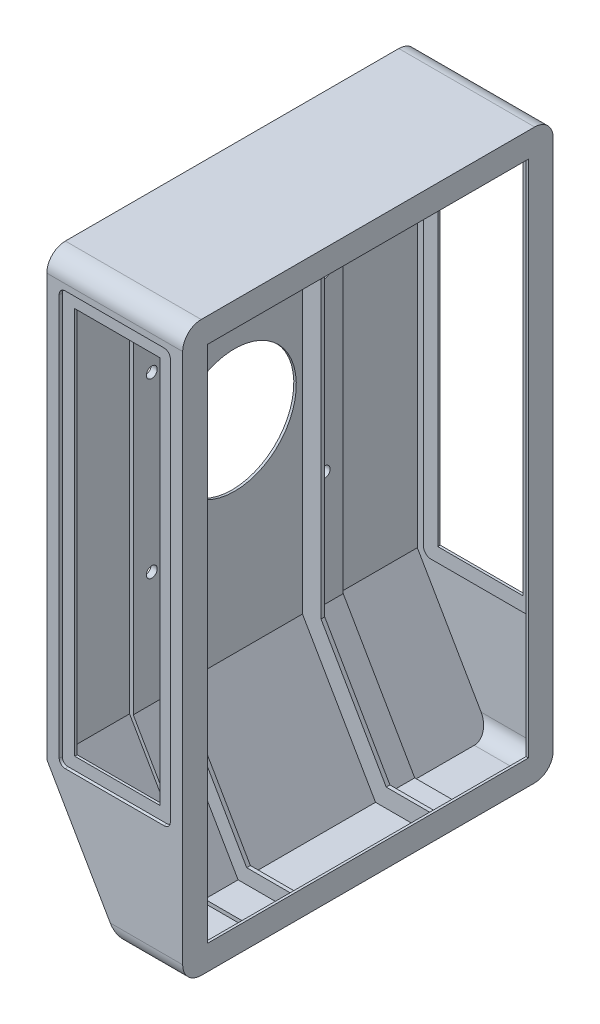
SolidWorks part; units mm, degrees
ref_plane "前视基准面" through (0, 0, 0) normal (0, 0, 1) x (1, 0, 0)
ref_plane "上视基准面" through (0, 0, 0) normal (0, 1, 0) x (1, 0, 0)
ref_plane "右视基准面" through (0, 0, 0) normal (1, 0, 0) x (0, 0, -1)
sketch "草图1" plane through (0, 0, 0) normal (0, 0, 1) x (1, 0, 0)
  line L1 (0, 227.2076) -> (-110, 227.2076)
  line L2 (0, 227.2076) -> (0, -232.7924)
  line L3 (0, -232.7924) -> (-110, -232.7924)
  line L4 (-110, 227.2076) -> (-110, -232.7924)
  dimension "D1" = 110
  dimension "D2" = 460
extrude "凸台-拉伸1" add sketch "草图1" against normal blind 300
chamfer "倒角1" distance 60 angle 60 1 edges at (-110, -232.7924, -150) first distance on face at (-55, -232.7924, -150)
chamfer "倒角2" [suppressed] distance 50 angle 30
ref_plane "基准面1" through (0, 0, -150) normal (0, 0, -1) x (-1, 0, 0)
ref_plane "基准面2" through (0, -2.7924, 0) normal (0, 1, 0) x (1, 0, 0)
fillet "圆角1" [suppressed] radius 20
fillet "圆角2" radius 15 4 edges at (-55, 227.2076, -300) (-25, -232.7924, -300) (-25, -232.7924, 0) (-55, 227.2076, 0)
sketch "草图2" plane through (0, 0, 0) normal (0, 0, 1) x (1, 0, 0)
  line L0 (0, -217.7924) -> (0, 212.2076) construction
  line L1 (-95, 207.2076) -> (-15, 207.2076)
  line L2 (-100, 202.2076) -> (-100, -122.7924)
  line L3 (-95, -127.7924) -> (-15, -127.7924)
  line L4 (-10, 202.2076) -> (-10, -122.7924)
  line L5 (-110, 212.2076) -> (-110, -128.8693) construction
  line L6 (-110, 227.2076) -> (0, 227.2076) construction
  arc A0 (-95, -127.7924) -> (-100, -122.7924) centre (-95, -122.7924) cw
  arc A1 (-15, -127.7924) -> (-10, -122.7924) centre (-15, -122.7924) ccw
  arc A2 (-100, 202.2076) -> (-95, 207.2076) centre (-95, 202.2076) cw
  arc A3 (-10, 202.2076) -> (-15, 207.2076) centre (-15, 202.2076) ccw
  point P14 (-10, -127.7924)
  point P19 (-10, 207.2076)
  dimension "D5" = 5
  dimension "D1" = 10
  dimension "D2" = 10
  dimension "D3" = 20
  dimension "D4" = 335
extrude "切除-拉伸1" cut sketch "草图2" against normal blind 2 draft 15
mirror "镜向1" about plane through (0, 0, -150) normal (0, 0, -1) of "切除-拉伸1"
shell "抽壳1" thickness 2
sketch "草图3" plane through (0, 0, 0) normal (1, 0, 0) x (0, 0, -1)
  line L2 (60.5, -2.7924) -> (-60.5, -2.7924) construction
  line L3 (20, -212.7924) -> (280, -212.7924)
  line L10 (20, -212.7924) -> (20, 207.2076)
  line L11 (20, 207.2076) -> (280, 207.2076)
  line L12 (280, -212.7924) -> (280, 207.2076)
  line L13 (20, -212.7924) -> (280, 207.2076) construction
  line L14 (20, 207.2076) -> (280, -212.7924) construction
  line L15 (150, -60.5) -> (150, 60.5) construction
  line L16 (285, 227.2076) -> (15, 227.2076) construction
  line L17 (300, -217.7924) -> (300, 212.2076) construction
  point P0 (150, -2.7924)
  dimension "D1" = 20
  dimension "D2" = 20
extrude "切除-拉伸2" cut sketch "草图3" against normal blind 3
sketch "草图4" plane through (0, 0, -298) normal (0, 0, -1) x (-1, 0, 0)
  line L0 (99.4641, 39.7076) -> (10.5359, 39.7076) construction
  line L1 (99.4641, 202.2076) -> (99.4641, -122.7924) construction
  line L2 (10.5359, -122.7924) -> (10.5359, 202.2076) construction
  line L3 (15, 206.6718) -> (95, 206.6718) construction
  line L4 (20.5359, -117.2565) -> (89.4641, -117.2565)
  line L5 (20.5359, -117.2565) -> (20.5359, 196.6718)
  line L6 (20.5359, 196.6718) -> (89.4641, 196.6718)
  line L7 (89.4641, -117.2565) -> (89.4641, 196.6718)
  line L8 (20.5359, -117.2565) -> (89.4641, 196.6718) construction
  line L9 (20.5359, 196.6718) -> (89.4641, -117.2565) construction
  point P6 (55, 39.7076)
  dimension "D1" = 10
  dimension "D2" = 10
extrude "切除-拉伸3" cut sketch "草图4" against normal blind 3
mirror "镜向2" about plane through (0, 0, -150) normal (0, 0, -1) of "切除-拉伸3"
ref_plane "基准面3" through (0, 0, -205) normal (0, 0, -1) x (-1, 0, 0)
sketch "草图6" plane through (0, 0, -205) normal (0, 0, -1) x (-1, 0, 0)
  line L6 (2, -230.7924) -> (48.8453, -230.7924)
  line L7 (48.8453, -230.7924) -> (108, -128.3334)
  line L8 (108, -128.3334) -> (108, 225.2076)
  line L9 (108, 225.2076) -> (2, 225.2076)
sketch "草图7" plane through (-2, 0, 0) normal (-1, 0, 0) x (0, 0, 1)
  line L0 (-15, -230.7924) -> (-285, -230.7924) construction
  line L1 (-235, -230.7924) -> (-205, -230.7924)
  line L2 (-235, -230.7924) -> (-235, -227.7924)
  line L3 (-208, -215.7924) -> (-205, -215.7924)
  line L4 (-205, -230.7924) -> (-205, -215.7924)
  line L5 (-205, -230.7924) -> (-205, -128.3334) construction
  line L9 (-235, -227.7924) -> (-208, -227.7924)
  line L10 (-208, -215.7924) -> (-208, -227.7924)
  dimension "D1" = 15
  dimension "D2" = 30
  dimension "D3" = 3
  dimension "D4" = 3
sweep "扫描2" add profiles "草图7" path "草图6"
mirror "镜向3" about plane through (0, 0, -150) normal (0, 0, -1) of "扫描2"
ref_plane "基准面4" through (0, 35.2076, 0) normal (0, 1, 0) x (1, 0, 0)
hole_wizard "M10x1.25 螺纹孔1" positions "草图9" profile "草图8" tap size "M10x1.25" standard "GB"
sketch "草图9" plane through (-110, 0, 0) normal (-1, 0, 0) x (0, 0, 1)
  line L0 (-150, 60.5) -> (-150, -60.5) construction
  line L2 (60.5, 35.2076) -> (-60.5, 35.2076) construction
  point P0 (-220, -34.7924)
  dimension "D1" = 70
  dimension "D2" = 70
sketch "草图8" plane through (-110, -34.7924, -220) normal (0, 1, 0) x (0, 0, 1)
  line L0 (0, 0) -> (0, 26.3938)
  line L1 (0, 26.3938) -> (4.4, 23.75)
  line L2 (4.4, 23.75) -> (4.4, 0)
  line L5 (4.4, 0) -> (0, 0)
  line L10 (0, 26.3938) -> (-4.4, 23.75) construction
  line L11 (0, -6.35) -> (0, 107.95) construction
  dimension "螺纹孔钻头直径" = 8.8
  dimension "螺纹孔钻头深度" = 23.75
  dimension "导头角度" = 118
cosmetic thread "孔螺蚊线1" parameters "D1"=5, "D2"=10
mirror "镜向4" about plane through (0, 0, -150) normal (0, 0, -1) of "M10x1.25 螺纹孔1"
mirror "镜向5" about plane through (0, 35.2076, 0) normal (0, 1, 0) of "镜向4"
sketch "草图10" plane through (-110, 0, 0) normal (-1, 0, 0) x (0, 0, 1)
  line L0 (-150, 60.5) -> (-150, -60.5) construction
  line L1 (60.5, 35.2076) -> (-60.5, 35.2076) construction
  line L2 (0, 212.2076) -> (0, -128.8693) construction
  line L3 (-300, 212.2076) -> (-300, -128.8693) construction
  circle A0 centre (-150, 35.2076) radius 50
  dimension "D1" = 100
extrude "切除-拉伸4" cut sketch "草图10" against normal blind 3
